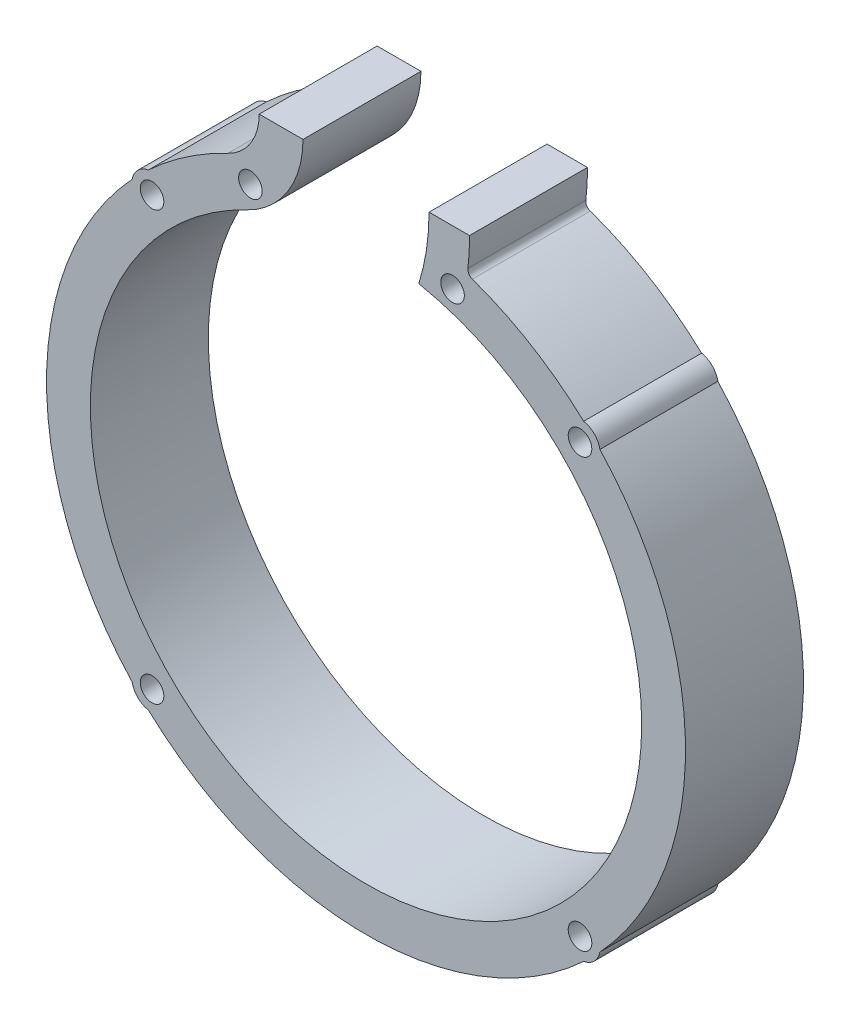
SolidWorks part; units mm, degrees
material "ABS"
ref_plane "前视基准面" through (0, 0, 0) normal (0, 0, 1) x (1, 0, 0)
ref_plane "上视基准面" through (0, 0, 0) normal (0, 1, 0) x (1, 0, 0)
ref_plane "右视基准面" through (0, 0, 0) normal (1, 0, 0) x (0, 0, -1)
sketch "草图1" plane through (0, 0, 0) normal (0, 0, 1) x (1, 0, 0)
  line L0 (-9.35, 50.0979) -> (9.35, 50.0979) construction
  line L1 (0, 50.0979) -> (0, 0) construction
  line L2 (-9.35, 50.0979) -> (-15.85, 50.0979)
  line L3 (9.35, 50.0979) -> (15.35, 50.0979)
  line L4 (0, 0) -> (12.8351, 41.9818) construction
  arc A0 (-17.6706, 36.8858) -> (7.8297, 40.1436) centre (0, 0) ccw
  arc A1 (-17.6706, 36.8858) -> (-9.35, 50.0979) centre (-24, 50.0979) ccw
  arc A2 (7.8297, 40.1436) -> (9.35, 50.0979) centre (-24, 50.0979) ccw
  arc A3 (-30.6806, 27.0465) -> (0, 50.0979) centre (-24, 50.0979) ccw construction
  arc A7 (15.1094, 45.753) -> (15.35, 50.0979) centre (-24, 50.0979) ccw
  circle A8 centre (0, 0) radius 34 construction
  arc A15 (15.7706, 44.6995) -> (-20.4788, 42.7478) centre (0, 0) cw
  circle A18 centre (0, 0) radius 43.9 construction
  circle A19 centre (12.8351, 41.9818) radius 1.75
  circle A20 centre (36.8176, 23.9097) radius 1.75 construction
  circle A21 centre (43.5728, -5.3501) radius 1.75 construction
  circle A22 centre (29.9397, -32.1064) radius 1.75 construction
  circle A23 centre (2.2975, -43.8398) radius 1.75 construction
  circle A24 centre (-26.4197, -35.0601) radius 1.75 construction
  circle A25 centre (-42.7748, -9.8754) radius 1.75 construction
  circle A26 centre (-39.1152, 19.9302) radius 1.75 construction
  circle A27 centre (-17.1531, 40.4102) radius 1.75
  arc A34 (15.7706, 44.6995) -> (15.1094, 45.753) centre (16.1033, 45.6426) cw
  arc A35 (-20.4788, 42.7478) -> (-15.85, 50.0979) centre (-24, 50.0979) ccw
  point P39 (0, 0)
  dimension "D1" = 81.8
  dimension "D3" = 24
  dimension "D4" = 1
  dimension "D5" = 6
  dimension "D6" = 68
  dimension "D7" = 3
  dimension "D8" = 6.5
  dimension "D10" = 9
  dimension "D11" = 17
  dimension "D13" = 3.5
  dimension "D2" = 9.35
  dimension "D14" = 9.35
extrude "凸台-拉伸1" add sketch "草图1" along normal blind 17.5
sketch "草图2" plane through (0, 0, 17.5) normal (0, 0, 1) x (1, 0, 0)
  circle A0 centre (0, 0) radius 44.9 construction
  circle A1 centre (-31.7491, 31.7491) radius 3
  circle A2 centre (31.7491, 31.7491) radius 3
  circle A3 centre (31.7491, -31.7491) radius 3
  circle A4 centre (-31.7491, -31.7491) radius 3
  point P15 (0, 0)
  dimension "D2" = 6
  dimension "D3" = 89.8
  dimension "D1" = 4
extrude "凸台-拉伸2" add sketch "草图2" against normal up to surface (17.5 mm away) up to face at (2.032, 26.4929, 0)
sketch "草图3" plane through (0, 0, 17.5) normal (0, 0, 1) x (1, 0, 0)
  circle A0 centre (-31.7491, 31.7491) radius 1.75
  circle A1 centre (-31.7491, -31.7491) radius 1.75
  circle A2 centre (31.7491, -31.7491) radius 1.75
  circle A3 centre (31.7491, 31.7491) radius 1.75
  dimension "D1" = 3.5
extrude "切除-拉伸1" cut sketch "草图3" against normal through all
